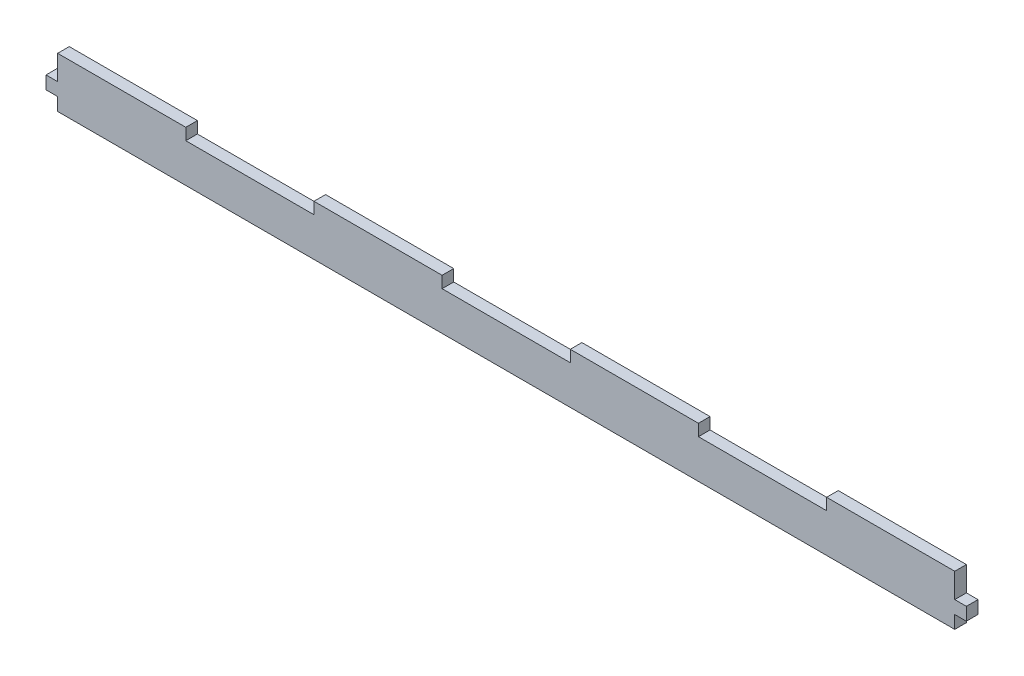
SolidWorks part; units mm, degrees
ref_plane "Front Plane" through (0, 0, 0) normal (0, 0, 1) x (1, 0, 0)
ref_plane "Top Plane" through (0, 0, 0) normal (0, 1, 0) x (1, 0, 0)
ref_plane "Right Plane" through (0, 0, 0) normal (1, 0, 0) x (0, 0, -1)
sketch "Sketch1" plane through (0, 0, 0) normal (0, 1, 0) x (1, 0, 0)
  line L1 (-207.5, -63.25) -> (207.5, -63.25)
  line L2 (-207.5, -63.25) -> (-207.5, 63.25)
  line L3 (-207.5, 63.25) -> (207.5, 63.25)
  line L4 (207.5, -63.25) -> (207.5, 63.25)
  line L5 (-207.5, -63.25) -> (207.5, 63.25) construction
  line L6 (-207.5, 63.25) -> (207.5, -63.25) construction
  point P0 (0, 0)
  dimension "D1" = 126.5
  dimension "D2" = 415
extrude "Boss-Extrude1" add sketch "Sketch1" along normal blind 6
sketch "Sketch2" plane through (0, 6, 0) normal (0, 1, 0) x (1, 0, 0)
  line L0 (213.5, -69.25) -> (213.5, 69.25)
  line L3 (-213.5, -69.25) -> (213.5, -69.25)
  line L4 (207.5, -63.25) -> (207.5, 63.25)
  line L5 (207.5, 63.25) -> (-207.5, 63.25)
  line L6 (-207.5, 63.25) -> (-207.5, -63.25)
  line L7 (-207.5, -63.25) -> (207.5, -63.25)
  line L8 (207.5, -63.25) -> (207.5, 63.25)
  line L9 (207.5, 63.25) -> (-207.5, 63.25)
  line L10 (-207.5, 63.25) -> (-207.5, -63.25)
  line L11 (-207.5, -63.25) -> (207.5, -63.25)
  line L12 (231.5, -87.25) -> (231.5, 87.25)
  line L13 (231.5, 87.25) -> (-231.5, 87.25)
  line L14 (-231.5, 87.25) -> (-231.5, -87.25)
  line L15 (-231.5, -87.25) -> (231.5, -87.25)
  line L16 (237.5, -93.25) -> (237.5, 93.25)
  line L19 (-237.5, -93.25) -> (237.5, -93.25)
  line L20 (213.5, 69.25) -> (-213.5, 69.25) construction
  line L21 (-213.5, 69.25) -> (-213.5, -69.25) construction
  line L22 (-213.5, -69.25) -> (-213.5, -63.25)
  line L27 (152.5, 69.25) -> (91.5, 69.25)
  line L28 (152.5, 69.25) -> (152.5, 63.25)
  line L29 (152.5, 63.25) -> (91.5, 63.25)
  line L30 (91.5, 69.25) -> (91.5, 63.25)
  line L31 (91.5, 69.25) -> (30.5, 69.25)
  line L32 (91.5, 69.25) -> (91.5, 63.25)
  line L33 (91.5, 63.25) -> (30.5, 63.25)
  line L34 (30.5, 69.25) -> (30.5, 63.25)
  line L35 (30.5, 69.25) -> (-30.5, 69.25)
  line L36 (30.5, 69.25) -> (30.5, 63.25)
  line L37 (30.5, 63.25) -> (-30.5, 63.25)
  line L38 (-30.5, 69.25) -> (-30.5, 63.25)
  line L39 (-30.5, 69.25) -> (-91.5, 69.25)
  line L40 (-30.5, 69.25) -> (-30.5, 63.25)
  line L41 (-30.5, 63.25) -> (-91.5, 63.25)
  line L42 (-91.5, 69.25) -> (-91.5, 63.25)
  line L43 (-91.5, 69.25) -> (-152.5, 69.25)
  line L44 (-91.5, 69.25) -> (-91.5, 63.25)
  line L45 (-91.5, 63.25) -> (-152.5, 63.25)
  line L46 (-152.5, 69.25) -> (-152.5, 63.25)
  line L47 (-152.5, 69.25) -> (-213.5, 69.25)
  line L48 (-152.5, 69.25) -> (-152.5, 63.25)
  line L49 (-152.5, 63.25) -> (-213.5, 63.25)
  line L50 (-213.5, 69.25) -> (-213.5, 63.25)
  line L51 (-213.5, 63.25) -> (-207.5, 63.25)
  line L52 (-213.5, 63.25) -> (-213.5, 37.95)
  line L53 (-213.5, 37.95) -> (-207.5, 37.95)
  line L54 (-207.5, 63.25) -> (-207.5, 37.95)
  line L55 (-207.5, 37.95) -> (-213.5, 37.95)
  line L56 (-207.5, 37.95) -> (-207.5, 12.65)
  line L57 (-207.5, 12.65) -> (-213.5, 12.65)
  line L58 (-213.5, 37.95) -> (-213.5, 12.65)
  line L59 (-213.5, 12.65) -> (-207.5, 12.65)
  line L60 (-213.5, 12.65) -> (-213.5, -12.65)
  line L61 (-213.5, -12.65) -> (-207.5, -12.65)
  line L62 (-207.5, 12.65) -> (-207.5, -12.65)
  line L63 (-207.5, -12.65) -> (-213.5, -12.65)
  line L64 (-207.5, -12.65) -> (-207.5, -37.95)
  line L65 (-207.5, -37.95) -> (-213.5, -37.95)
  line L66 (-213.5, -12.65) -> (-213.5, -37.95)
  line L67 (-213.5, -37.95) -> (-207.5, -37.95)
  line L68 (-213.5, -37.95) -> (-213.5, -63.25)
  line L69 (-213.5, -63.25) -> (-207.5, -63.25)
  line L70 (-207.5, -37.95) -> (-207.5, -63.25)
  line L71 (152.5, 63.25) -> (213.5, 63.25)
  line L72 (152.5, 63.25) -> (152.5, 69.25)
  line L73 (152.5, 69.25) -> (213.5, 69.25)
  line L74 (213.5, 63.25) -> (213.5, 69.25)
  line L75 (-237.5, 93.25) -> (-231.5, 93.25)
  line L76 (-237.5, 93.25) -> (-237.5, 55.95)
  line L77 (-237.5, 55.95) -> (-231.5, 55.95)
  line L78 (-231.5, 93.25) -> (-231.5, 55.95)
  line L79 (-237.5, 93.25) -> (-237.5, -93.25) construction
  line L80 (-231.5, 55.95) -> (-237.5, 55.95)
  line L81 (-231.5, 55.95) -> (-231.5, 18.65)
  line L82 (-231.5, 18.65) -> (-237.5, 18.65)
  line L83 (-237.5, 55.95) -> (-237.5, 18.65)
  line L84 (-237.5, 18.65) -> (-231.5, 18.65)
  line L85 (-237.5, 18.65) -> (-237.5, -18.65)
  line L86 (-237.5, -18.65) -> (-231.5, -18.65)
  line L87 (-231.5, 18.65) -> (-231.5, -18.65)
  line L88 (-231.5, -18.65) -> (-237.5, -18.65)
  line L89 (-231.5, -18.65) -> (-231.5, -55.95)
  line L90 (-231.5, -55.95) -> (-237.5, -55.95)
  line L91 (-237.5, -18.65) -> (-237.5, -55.95)
  line L92 (-237.5, -55.95) -> (-231.5, -55.95)
  line L93 (-237.5, -55.95) -> (-237.5, -93.25)
  line L94 (-237.5, -93.25) -> (-231.5, -93.25)
  line L95 (-231.5, -55.95) -> (-231.5, -93.25)
  line L96 (231.5, 87.25) -> (165.3571, 87.25)
  line L97 (231.5, 87.25) -> (231.5, 93.25)
  line L98 (231.5, 93.25) -> (165.3571, 93.25)
  line L99 (165.3571, 87.25) -> (165.3571, 93.25)
  line L100 (165.3571, 93.25) -> (99.2143, 93.25)
  line L101 (165.3571, 93.25) -> (165.3571, 87.25)
  line L102 (165.3571, 87.25) -> (99.2143, 87.25)
  line L103 (99.2143, 93.25) -> (99.2143, 87.25)
  line L104 (99.2143, 87.25) -> (33.0714, 87.25)
  line L105 (99.2143, 87.25) -> (99.2143, 93.25)
  line L106 (99.2143, 93.25) -> (33.0714, 93.25)
  line L107 (33.0714, 87.25) -> (33.0714, 93.25)
  line L108 (33.0714, 93.25) -> (-33.0714, 93.25)
  line L109 (33.0714, 93.25) -> (33.0714, 87.25)
  line L110 (33.0714, 87.25) -> (-33.0714, 87.25)
  line L111 (-33.0714, 93.25) -> (-33.0714, 87.25)
  line L112 (-33.0714, 87.25) -> (-99.2143, 87.25)
  line L113 (-33.0714, 87.25) -> (-33.0714, 93.25)
  line L114 (-33.0714, 93.25) -> (-99.2143, 93.25)
  line L115 (-99.2143, 87.25) -> (-99.2143, 93.25)
  line L116 (-99.2143, 93.25) -> (-165.3571, 93.25)
  line L117 (-99.2143, 93.25) -> (-99.2143, 87.25)
  line L118 (-99.2143, 87.25) -> (-165.3571, 87.25)
  line L119 (-165.3571, 93.25) -> (-165.3571, 87.25)
  line L120 (-165.3571, 87.25) -> (-231.5, 87.25)
  line L121 (-165.3571, 87.25) -> (-165.3571, 93.25)
  line L122 (-165.3571, 93.25) -> (-231.5, 93.25)
  line L123 (-231.5, 87.25) -> (-231.5, 93.25)
  line L124 (237.5, 93.25) -> (-237.5, 93.25) construction
  line L125 (237.5, 93.25) -> (231.5, 93.25)
  dimension "D1" = 0
  dimension "D2" = 6
  dimension "D3" = 18
  dimension "D4" = 6
extrude "Boss-Extrude2" add sketch "Sketch2" against normal blind 20 contours L119 L122 L78 L13 | L116 L119 L13 L115 | L115 L13 L111 L114 | L108 L111 L13 L107 | L107 L13 L103 L106 | L100 L103 L13 L99 | L99 L13 L97 L98 region at (198.4286, 6, -90.25) region at (132.2857, 6, -90.25) region at (66.1429, 6, -90.25) region at (0, 6, -90.25) region at (-66.1429, 6, -90.25) region at (-132.2857, 6, -90.25) region at (-198.4286, 6, -90.25)
extrude "Cut-Extrude1" cut sketch "Sketch1<2>" against normal through all both and the other way through all
sketch "Sketch1<2>" plane through (0, 0, 0) normal (0, 1, 0) x (1, 0, 0) same geometry as "Sketch1"
extrude "Boss-Extrude3" add sketch "Sketch2<4>" along normal blind 6 contours L119 L122 L78 L13 | L115 L13 L111 L114 | L107 L13 L103 L106 | L99 L13 L97 L98 region at (198.4286, 6, -90.25) region at (66.1429, 6, -90.25) region at (-66.1429, 6, -90.25) region at (-198.4286, 6, -90.25)
sketch "Sketch2<4>" plane through (0, 6, 0) normal (0, 1, 0) x (1, 0, 0) same geometry as "Sketch2"
sketch "Sketch4" plane through (-231.5, 0, 0) normal (-1, 0, 0) x (0, 0, 1)
  line L0 (-93.25, -14) -> (-93.25, 12) construction
  line L1 (-87.25, -14) -> (-93.25, -14)
  line L2 (-87.25, -14) -> (-87.25, -7.3333)
  line L3 (-87.25, -7.3333) -> (-93.25, -7.3333)
  line L4 (-93.25, -14) -> (-93.25, -7.3333)
  line L5 (-87.25, -14) -> (-87.25, 12) construction
  line L6 (-93.25, -7.3333) -> (-87.25, -7.3333)
  line L7 (-93.25, -7.3333) -> (-93.25, -0.6667)
  line L8 (-93.25, -0.6667) -> (-87.25, -0.6667)
  line L9 (-87.25, -7.3333) -> (-87.25, -0.6667)
  line L10 (-93.25, 6) -> (-55.95, 6) construction
  line L11 (-87.25, -0.6667) -> (-93.25, -0.6667)
  line L12 (-87.25, -0.6667) -> (-87.25, 6)
  line L13 (-87.25, 6) -> (-93.25, 6)
  line L14 (-93.25, -0.6667) -> (-93.25, 6)
  line M7 (-87.25, -14) -> (-87.25, 12)
  line M9 (-93.25, 12) -> (-93.25, -14)
extrude "Boss-Extrude4" add sketch "Sketch4" along normal blind 6 contours L8 L3 M9 M7 region at (-231.5, -4, -90.25)
mirror "Mirror2" about plane through (0, 0, 0) normal (1, 0, 0) of "Boss-Extrude4"
